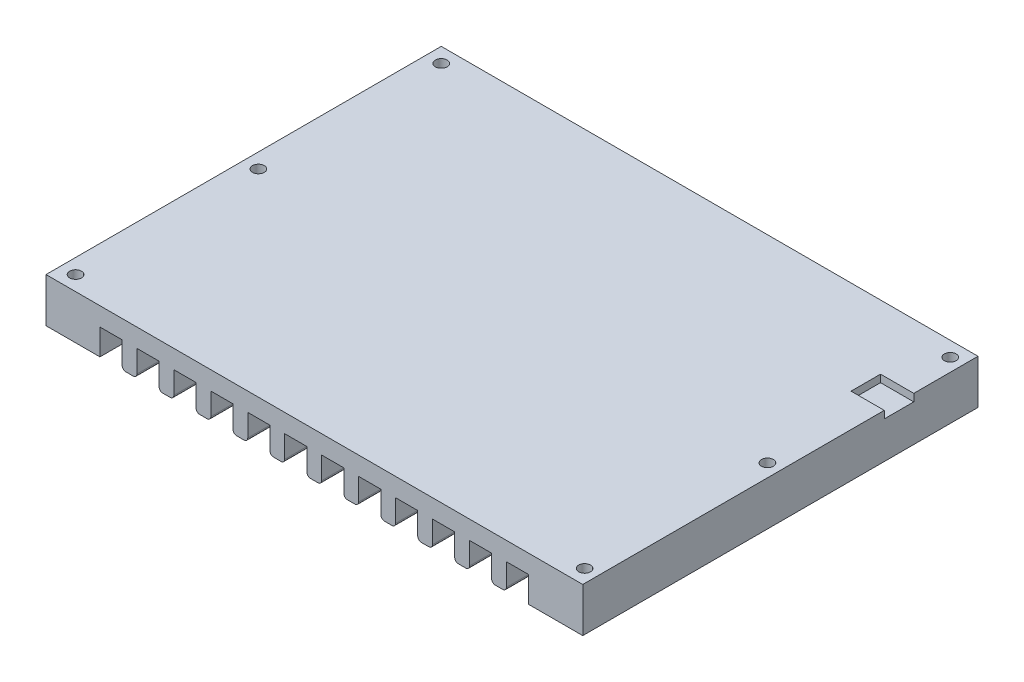
SolidWorks part; units mm, degrees
material "1060-H12"
ref_plane "前视基准面" through (0, 0, 0) normal (0, 0, 1) x (1, 0, 0)
ref_plane "上视基准面" through (0, 0, 0) normal (0, 1, 0) x (1, 0, 0)
ref_plane "右视基准面" through (0, 0, 0) normal (1, 0, 0) x (0, 0, -1)
other "Configuration Table"
sketch "草图1" plane through (0, 0, 0) normal (0, 1, 0) x (1, 0, 0)
  line L0 (0, 0) -> (72.63, 0)
  line L1 (0, 0) -> (0, 53.48)
  line L2 (0, 53.48) -> (72.63, 53.48)
  line L3 (72.63, 53.48) -> (72.63, 44.79)
  line L4 (72.63, 0) -> (72.63, 40.8)
  line L5 (72.63, 44.79) -> (68.13, 44.79)
  line L6 (72.63, 40.8) -> (68.13, 40.8)
  line L7 (68.13, 40.8) -> (68.13, 44.79)
  line L8 (72.63, 44.79) -> (72.63, 40.8)
  circle A1 centre (2, 2) radius 0.8
  circle A2 centre (70.879, 2) radius 0.8
  circle A3 centre (2, 51.48) radius 0.8
  circle A4 centre (70.879, 51.48) radius 0.8
  circle A5 centre (2, 26.74) radius 0.8
  circle A6 centre (70.879, 26.74) radius 0.8
  dimension "D2" = 53.48
  dimension "D3" = 72.63
extrude "凸台-拉伸2" add sketch "草图1" against normal blind 6 contours L3 L8 L4 L0 L1 L2
extrude "切除-拉伸1" cut sketch "草图1<6>" against normal blind 1 contours L5 L7 L6 L8
sketch "草图1<6>" plane through (0, 0, 0) normal (0, 1, 0) x (1, 0, 0) same geometry as "草图1"
extrude "切除-拉伸2" cut sketch "草图1<7>" against normal blind 6 contours A1 | A2 | A3 | A4
sketch "草图1<7>" plane through (0, 0, 0) normal (0, 1, 0) x (1, 0, 0) same geometry as "草图1"
cosmetic thread "装饰螺纹线2" parameters "D2"=2
cosmetic thread "装饰螺纹线3" parameters "D2"=2
cosmetic thread "装饰螺纹线4" parameters "D2"=2
cosmetic thread "装饰螺纹线5" parameters "D2"=2
extrude "切除-拉伸3" cut sketch "草图1<8>" against normal blind 6 contours A6 | A5
sketch "草图1<8>" plane through (0, 0, 0) normal (0, 1, 0) x (1, 0, 0) same geometry as "草图1"
cosmetic thread "装饰螺纹线6" parameters "D2"=2
cosmetic thread "装饰螺纹线7" parameters "D2"=2
sketch "草图2" plane through (0, 0, 0) normal (0, 0, 1) x (1, 0, 0)
  line L0 (0, -6) -> (7.3, -6)
  line L1 (0, -6) -> (72.63, -6) construction
  line L2 (72.63, -6) -> (65.3, -6)
  line L3 (7.3, -6) -> (7.3, -2.5)
  line L4 (7.3, -2.5) -> (10.3, -2.5)
  line L5 (10.3, -2.5) -> (10.3, -6)
  line L6 (10.3, -6) -> (12.3, -6)
  line L7 (12.3, -6) -> (12.3, -2.5)
  line L8 (12.3, -2.5) -> (15.3, -2.5)
  line L9 (15.3, -2.5) -> (15.3, -6)
  line L10 (15.3, -6) -> (17.3, -6)
  line L11 (17.3, -6) -> (17.3, -2.5)
  line L12 (17.3, -2.5) -> (20.3, -2.5)
  line L13 (20.3, -2.5) -> (20.3, -6)
  line L14 (20.3, -6) -> (22.3, -6)
  line L15 (22.3, -6) -> (22.3, -2.5)
  line L16 (22.3, -2.5) -> (25.3, -2.5)
  line L17 (25.3, -2.5) -> (25.3, -6)
  line L18 (25.3, -6) -> (27.3, -6)
  line L19 (27.3, -6) -> (27.3, -2.5)
  line L20 (27.3, -2.5) -> (30.3, -2.5)
  line L21 (30.3, -2.5) -> (30.3, -6)
  line L22 (30.3, -6) -> (32.3, -6)
  line L23 (32.3, -6) -> (32.3, -2.5)
  line L24 (32.3, -2.5) -> (35.3, -2.5)
  line L25 (35.3, -2.5) -> (35.3, -6)
  line L26 (35.3, -6) -> (37.3, -6)
  line L27 (37.3, -6) -> (37.3, -2.5)
  line L28 (37.3, -2.5) -> (40.3, -2.5)
  line L29 (40.3, -2.5) -> (40.3, -6)
  line L30 (40.3, -6) -> (42.3, -6)
  line L31 (42.3, -6) -> (42.3, -2.5)
  line L32 (42.3, -2.5) -> (45.3, -2.5)
  line L33 (45.3, -2.5) -> (45.3, -6)
  line L34 (45.3, -6) -> (47.3, -6)
  line L35 (47.3, -6) -> (47.3, -2.5)
  line L36 (47.3, -2.5) -> (50.3, -2.5)
  line L37 (50.3, -2.5) -> (50.3, -6)
  line L38 (50.3, -6) -> (52.3, -6)
  line L39 (52.3, -6) -> (52.3, -2.5)
  line L40 (52.3, -2.5) -> (55.3, -2.5)
  line L41 (55.3, -2.5) -> (55.3, -6)
  line L42 (55.3, -6) -> (57.3, -6)
  line L43 (57.3, -6) -> (57.3, -2.5)
  line L44 (57.3, -2.5) -> (60.3, -2.5)
  line L45 (60.3, -2.5) -> (60.3, -6)
  line L46 (60.3, -6) -> (62.3, -6)
  line L47 (62.3, -6) -> (62.3, -2.5)
  line L48 (62.3, -2.5) -> (65.3, -2.5)
  line L49 (65.3, -2.5) -> (65.3, -6)
  line L50 (7.3, -6) -> (10.3, -6)
  line L51 (12.3, -6) -> (15.3, -6)
  line L52 (17.3, -6) -> (20.3, -6)
  line L53 (22.3, -6) -> (25.3, -6)
  line L54 (27.3, -6) -> (30.3, -6)
  line L55 (32.3, -6) -> (35.3, -6)
  line L56 (37.3, -6) -> (40.3, -6)
  line L57 (42.3, -6) -> (45.3, -6)
  line L58 (47.3, -6) -> (50.3, -6)
  line L59 (52.3, -6) -> (55.3, -6)
  line L60 (57.3, -6) -> (60.3, -6)
  line L61 (62.3, -6) -> (65.3, -6)
  line M8 (0, -6) -> (72.63, -6)
extrude "切除-拉伸5" cut sketch "草图2" against normal blind 60 contours L5 L4 L3 M8 | L9 L8 L7 M8 | L13 L12 L11 M8 | L17 L16 L15 M8 | L21 L20 L19 M8 | L25 L24 L23 M8 | L29 L28 L27 M8 | L33 L32 L31 M8 | L37 L36 L35 M8 | L41 L40 L39 M8 | L45 L44 L43 M8 | L49 L48 L47 M8 region at (63.8, -4.25, 0) region at (58.8, -4.25, 0) region at (53.8, -4.25, 0) region at (48.8, -4.25, 0) region at (43.8, -4.25, 0) region at (38.8, -4.25, 0) region at (33.8, -4.25, 0) region at (28.8, -4.25, 0) region at (23.8, -4.25, 0) region at (18.8, -4.25, 0) region at (13.8, -4.25, 0) region at (8.8, -4.25, 0)
fillet "圆角1" radius 0.5 22 edges at (12.3, -6, -26.74) (10.3, -6, -26.74) (15.3, -6, -26.74) (17.3, -6, -26.74) (20.3, -6, -26.74) (22.3, -6, -26.74) (25.3, -6, -26.74) (27.3, -6, -26.74) (30.3, -6, -26.74) (32.3, -6, -26.74) (35.3, -6, -26.74) (37.3, -6, -26.74) (40.3, -6, -26.74) (42.3, -6, -26.74) (45.3, -6, -26.74) (47.3, -6, -26.74) (50.3, -6, -26.74) (52.3, -6, -26.74) (55.3, -6, -26.74) (57.3, -6, -26.74) (60.3, -6, -26.74) (62.3, -6, -26.74)
